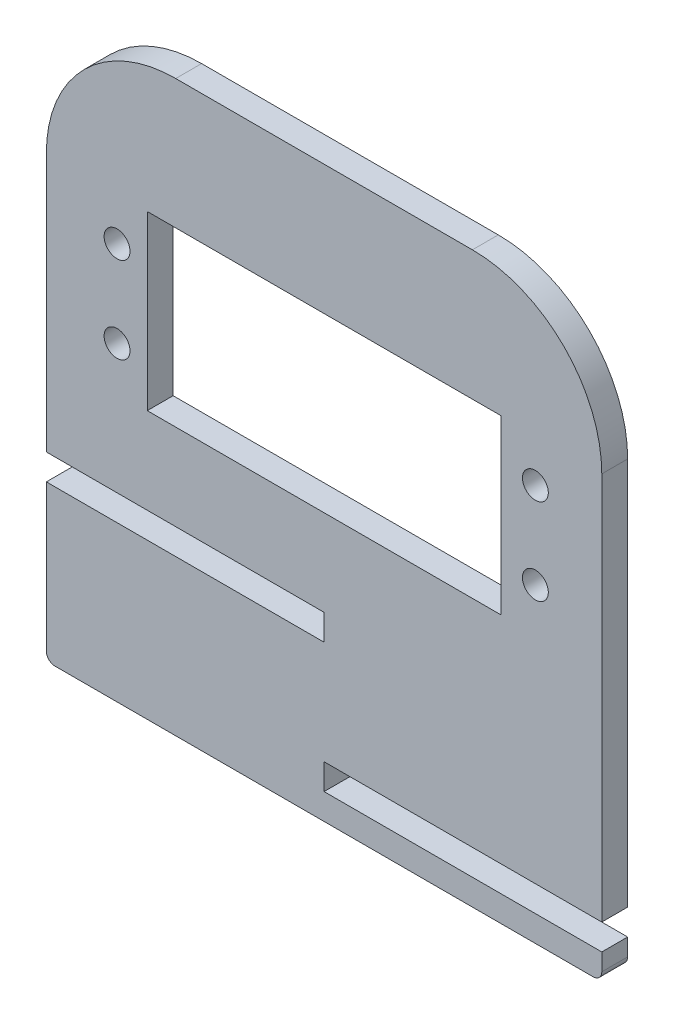
SolidWorks part; units mm, degrees
ref_plane "Front Plane" through (0, 0, 0) normal (0, 0, 1) x (1, 0, 0)
ref_plane "Top Plane" through (0, 0, 0) normal (0, 1, 0) x (1, 0, 0)
ref_plane "Right Plane" through (0, 0, 0) normal (1, 0, 0) x (0, 0, -1)
sketch "Sketch1" plane through (0, 0, 0) normal (0, 0, 1) x (1, 0, 0)
  line L0 (-49.6615, -6.4209) -> (-15.2615, -6.4209)
  line L8 (-52.9615, -21.4209) -> (-11.9615, -21.4209)
  line L9 (-52.9615, -21.4209) -> (-52.9615, -41.4209)
  line L10 (-52.9615, -41.4209) -> (-11.9615, -41.4209)
  line L11 (-11.9615, -21.4209) -> (-11.9615, -41.4209)
  line L12 (-64.6615, -21.4209) -> (-64.6615, -51.4209)
  line L13 (-64.6615, -51.4209) -> (-32.4615, -51.4209)
  line L15 (-64.6615, -54.4209) -> (-32.4615, -54.4209)
  line L16 (-32.4615, -51.4209) -> (-32.4615, -54.4209)
  line L17 (-0.2615, -66.4209) -> (-32.4615, -66.4209)
  line L19 (-0.2615, -69.4209) -> (-32.4615, -69.4209)
  line L20 (-32.4615, -66.4209) -> (-32.4615, -69.4209)
  line L21 (-64.6615, -54.4209) -> (-64.6615, -71.4209)
  line L22 (-0.2615, -21.4209) -> (-0.2615, -66.4209)
  line L23 (-0.2615, -69.4209) -> (-0.2615, -71.4209)
  line L24 (-63.6615, -72.4209) -> (-1.2615, -72.4209)
  arc A0 (-15.2615, -6.4209) -> (-0.2615, -21.4209) centre (-15.2615, -21.4209) cw
  arc A2 (-49.6615, -6.4209) -> (-64.6615, -21.4209) centre (-49.6615, -21.4209) ccw
  arc A3 (-64.6615, -71.4209) -> (-63.6615, -72.4209) centre (-63.6615, -71.4209) ccw
  arc A4 (-1.2615, -72.4209) -> (-0.2615, -71.4209) centre (-1.2615, -71.4209) ccw
  point P28 (-32.4615, -6.4209)
  point P29 (-32.4615, -21.4209)
  dimension "D1" = 41
  dimension "D9" = 64.4
  dimension "D2" = 20
  dimension "D3" = 15
  dimension "D4" = 30
  dimension "D5" = 15
  dimension "D6" = 2
  dimension "D7" = 32.2
  dimension "D8" = 3
  dimension "D10" = 32.2
  dimension "D11" = 3
extrude "Boss-Extrude7" add sketch "Sketch1" along normal blind 3 contours L11 L8 L9 L10 | L23 A4 L24 A3 L21 L15 L16 L13 L12 A2 L0 A0 L22 L17 L20 L19 region at (-32.4615, -31.4209, 0)
sketch "Sketch2" plane through (0, 0, 3) normal (0, 0, 1) x (1, 0, 0)
  line L0 (-52.9615, -21.4209) -> (-11.9615, -21.4209) construction
  circle A0 centre (-7.9615, -36.421) radius 1.5
  circle A2 centre (-7.9615, -26.421) radius 1.5
  circle A3 centre (-56.4615, -26.421) radius 1.5
  circle A4 centre (-56.4615, -36.421) radius 1.5
  point P8 (0, 0)
  point P9 (0, 0)
  point P10 (0, 0)
  point P11 (0, 0)
  point P12 (0, 0)
  point P15 (-32.4615, -21.4209)
  dimension "D1" = 10
  dimension "D2" = 48.5
  dimension "D3" = 24
  dimension "D4" = 5.0001
extrude "Cut-Extrude1" cut sketch "Sketch2" against normal blind 3
